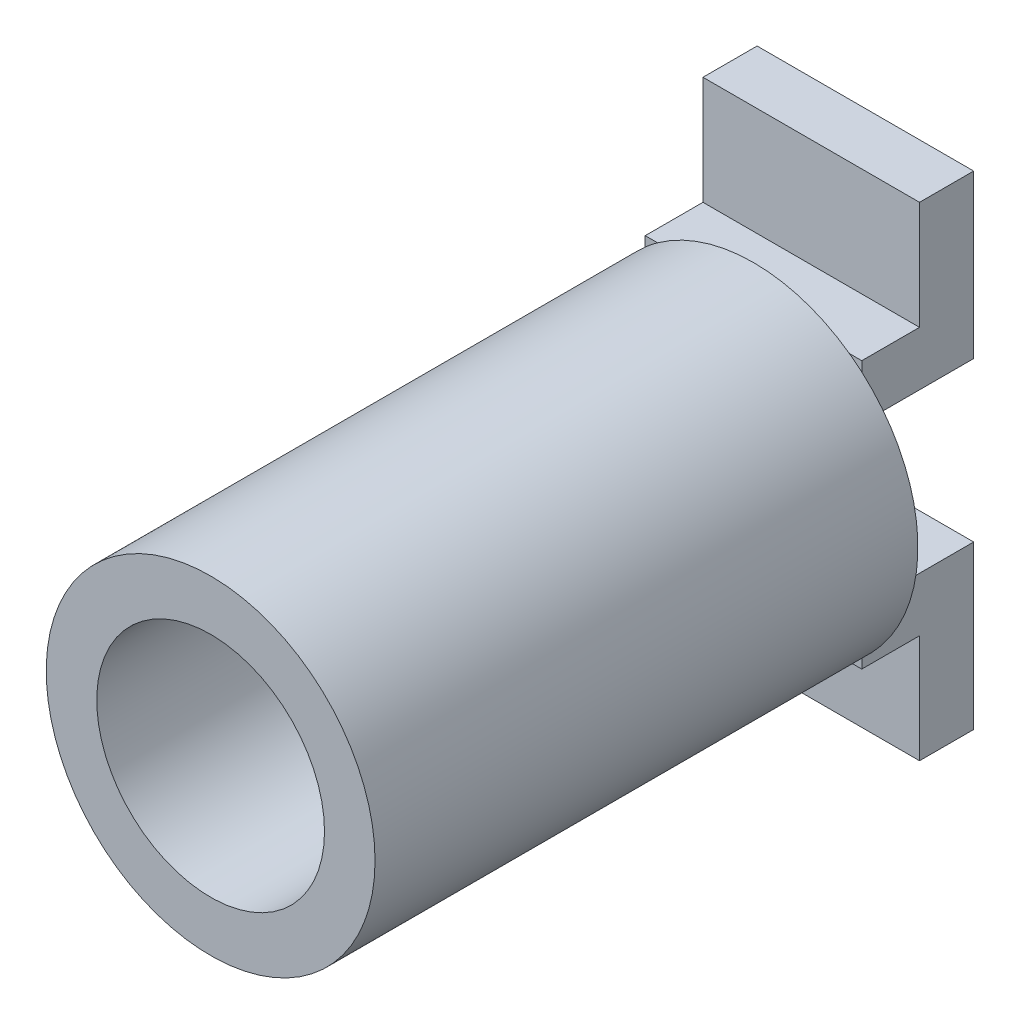
SolidWorks part; units mm, degrees
ref_plane "Front Plane" through (0, 0, 0) normal (0, 0, 1) x (1, 0, 0)
ref_plane "Top Plane" through (0, 0, 0) normal (0, 1, 0) x (1, 0, 0)
ref_plane "Right Plane" through (0, 0, 0) normal (1, 0, 0) x (0, 0, -1)
sketch "Sketch1" plane through (0, 0, 0) normal (0, 0, 1) x (1, 0, 0)
  circle A2 centre (-7.6717, 4.7989) radius 4.555
  circle A4 centre (-7.6717, 4.7989) radius 3.155
  circle A5 centre (-7.6717, 4.7989) radius 3.155
  dimension "D1" = 0.1
extrude "Boss-Extrude1" add sketch "Sketch1" along normal up to surface (7.64 mm away)
sketch "Sketch7" plane through (0, 0, 7.64) normal (0, 0, 1) x (1, 0, 0)
  line L0 (-12.2267, 4.7989) -> (-3.1167, 4.7989) construction
  circle A0 centre (-7.6717, 4.7989) radius 4.555 construction
ref_plane "Plane1" through (0, 4.7989, 0) normal (0, -1, 0) x (1, 0, 0)
sketch "Sketch2" plane through (0, 0, 0) normal (0, 0, -1) x (-1, 0, 0)
  line L4 (10.8417, 5.2839) -> (4.5017, 5.2839)
  line L5 (4.5017, 5.2839) -> (4.5017, 3.5839)
  line L6 (4.5017, 3.5839) -> (10.8417, 3.5839)
  line L7 (10.8417, 3.5839) -> (10.8417, 5.2839)
  line L8 (10.8417, 5.2839) -> (4.5017, 5.2839)
  line L9 (4.5017, 5.2839) -> (4.5017, 3.5839)
  line L10 (4.5017, 3.5839) -> (10.8417, 3.5839)
  line L11 (10.8417, 3.5839) -> (10.8417, 5.2839)
  circle A0 centre (7.6717, 4.7989) radius 3.155 construction
  circle A1 centre (7.6717, 4.7989) radius 3.155
  circle M5 centre (7.6717, 4.7989) radius 4.555
  circle M6 centre (7.6717, 4.7989) radius 3.155
  dimension "D1" = 0
extrude "Boss-Extrude2" add sketch "Sketch2" along normal up to surface (5.9 mm away) contours L11 L10 L9 L8 M5 M6 region at (-3.2455, 4.7989, 0)
sketch "Sketch3" plane through (0, 0, -5.9) normal (0, 0, -1) x (-1, 0, 0)
  line L0 (7.6717, 7.7989) -> (7.6717, 1.7989) construction
  line L1 (7.6717, 9.3539) -> (7.6717, 0.2439)
  circle A0 centre (7.6717, 4.7989) radius 4.555 construction
  circle A1 centre (7.6717, 4.7989) radius 4.555
  line M1 (10.8417, 5.2839) -> (10.8417, 3.5839)
  line M2 (10.8417, 3.5839) -> (10.5834, 3.5839)
  arc M3 (10.5834, 3.5839) -> (4.76, 3.5839) centre (7.6717, 4.7989) cw
  line M4 (4.76, 3.5839) -> (4.5017, 3.5839)
  line M5 (4.5017, 3.5839) -> (4.5017, 5.2839)
  line M6 (4.5017, 5.2839) -> (4.5542, 5.2839)
  arc M7 (4.5542, 5.2839) -> (10.7892, 5.2839) centre (7.6717, 4.7989) cw
  line M8 (10.7892, 5.2839) -> (10.8417, 5.2839)
  circle M9 centre (7.6717, 4.7989) radius 4.555
extrude "Boss-Extrude3" add sketch "Sketch3" along normal blind 1.5 contours L1 M9 M7 M8 M1 M2 M3 | L1 M7 M3 M2 M1 M8 | L1 M9 M3 M4 M5 M6 M7 region at (-10.8206, 7.9477, -5.9) region at (-7.5699, 8.6539, -5.9) region at (-9.0251, 4.7928, -5.9)
sketch "Sketch4" plane through (0, 0, -7.4) normal (0, 0, -1) x (-1, 0, 0)
  line L0 (10.6717, 4.7989) -> (4.6717, 4.7989) construction
  line L1 (7.6717, 8.4989) -> (10.6717, 8.4989)
  line L2 (7.6717, 8.4989) -> (7.6717, 1.0989)
  line L3 (7.6717, 1.0989) -> (10.6717, 1.0989)
  line L4 (10.6717, 8.4989) -> (10.6717, 1.0989)
  line L5 (7.6717, 8.4989) -> (10.6717, 1.0989) construction
  line L6 (7.6717, 1.0989) -> (10.6717, 8.4989) construction
  line L7 (7.6717, 7.9539) -> (7.6717, 1.6439) construction
  line L8 (6.1717, 6.9989) -> (6.1717, 8.4989) construction
  line L9 (4.6717, 8.4989) -> (7.6717, 8.4989)
  line L10 (4.6717, 8.4989) -> (4.6717, 1.0989)
  line L11 (4.6717, 1.0989) -> (7.6717, 1.0989)
  line L12 (7.6717, 8.4989) -> (7.6717, 1.0989)
  line L13 (4.6717, 8.4989) -> (7.6717, 1.0989) construction
  line L14 (4.6717, 1.0989) -> (7.6717, 8.4989) construction
  line L15 (10.6717, 8.4989) -> (12.1717, 8.4989)
  line L16 (10.6717, 8.4989) -> (10.6717, 6.4989)
  line L17 (10.6717, 6.4989) -> (12.1717, 6.4989)
  line L18 (12.1717, 8.4989) -> (12.1717, 6.4989)
  line L19 (10.6717, 1.0989) -> (12.1717, 1.0989)
  line L20 (10.6717, 1.0989) -> (10.6717, 3.0989)
  line L21 (10.6717, 3.0989) -> (12.1717, 3.0989)
  line L22 (12.1717, 1.0989) -> (12.1717, 3.0989)
  line L23 (4.6717, 1.0989) -> (3.1717, 1.0989)
  line L24 (4.6717, 1.0989) -> (4.6717, 3.0989)
  line L25 (4.6717, 3.0989) -> (3.1717, 3.0989)
  line L26 (3.1717, 1.0989) -> (3.1717, 3.0989)
  line L27 (4.6717, 8.4989) -> (3.1717, 8.4989)
  line L28 (4.6717, 8.4989) -> (4.6717, 6.4989)
  line L29 (4.6717, 6.4989) -> (3.1717, 6.4989)
  line L30 (3.1717, 8.4989) -> (3.1717, 6.4989)
  line L31 (4.6717, 1.0989) -> (7.6717, 1.0989)
  line L32 (4.6717, 1.0989) -> (4.6717, 2.5989)
  line L33 (4.6717, 2.5989) -> (7.6717, 2.5989)
  line L34 (7.6717, 1.0989) -> (7.6717, 2.5989)
  line L35 (4.6717, 8.4989) -> (7.6717, 8.4989)
  line L36 (4.6717, 8.4989) -> (4.6717, 6.9989)
  line L37 (4.6717, 6.9989) -> (7.6717, 6.9989)
  line L38 (7.6717, 8.4989) -> (7.6717, 6.9989)
  line L39 (6.1717, 2.5989) -> (6.1717, 1.0989) construction
  point P0 (9.1717, 4.7989)
  point P9 (6.1717, 4.7989)
  circle M18 centre (7.6717, 4.7989) radius 4.555
  line M19 (7.6717, 7.9539) -> (7.6717, 1.6439)
  arc M44 (4.5542, 5.2839) -> (7.6717, 7.9539) centre (7.6717, 4.7989) cw
  arc M45 (7.6717, 1.6439) -> (4.76, 3.5839) centre (7.6717, 4.7989) cw
  dimension "D1" = 3
  dimension "D2" = 7.4
  dimension "D3" = 3.4
  dimension "D4" = 1.5
extrude "Boss-Extrude4" add sketch "Sketch4" along normal blind 3.1 contours L4 L1 L12 L3 M18 M19 | L10 L37 L9 M19 | L33 L24 L11 L12 | L4 L1 M18 | L4 L3 M18 | L9 L10 M18 | L10 L11 M18 | L33 L12 M45 | L37 M44 M19 region at (-9.166, 4.7989, -7.4) region at (-5.8754, 7.921, -7.4) region at (-10.5592, 8.4096, -7.4) region at (-6.8035, 7.3863, -7.4) region at (-4.7842, 8.4096, -7.4) region at (-6.8035, 2.2115, -7.4) region at (-5.8754, 1.6768, -7.4) region at (-10.5592, 1.1882, -7.4) region at (-4.7842, 1.1882, -7.4)
sketch "Sketch5" plane through (0, 8.4989, 0) normal (0, 1, 0) x (1, 0, 0)
  line L0 (-10.6717, 10.5) -> (-10.6717, 7.4) construction
  line L1 (-10.6717, 9) -> (-4.6717, 9)
  line L2 (-10.6717, 9) -> (-10.6717, 10.5)
  line L3 (-10.6717, 10.5) -> (-4.6717, 10.5)
  line L4 (-4.6717, 9) -> (-4.6717, 10.5)
  dimension "D1" = 1.5
extrude "Boss-Extrude5" add sketch "Sketch5" along normal blind 3
mirror "Mirror1" about plane through (0, 4.7989, 0) normal (0, -1, 0) of "Boss-Extrude5"
equation "\"D3@Sketch4\"=3.00mm+.2*2"
